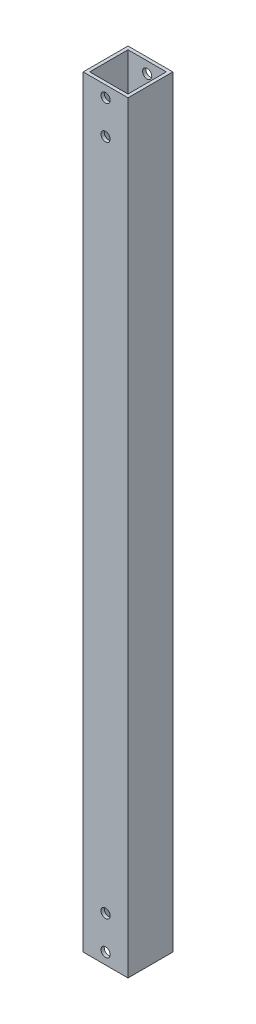
SolidWorks part; units mm, degrees
ref_plane "Front Plane" through (0, 0, 0) normal (0, 0, 1) x (1, 0, 0)
ref_plane "Top Plane" through (0, 0, 0) normal (0, 1, 0) x (1, 0, 0)
ref_plane "Right Plane" through (0, 0, 0) normal (1, 0, 0) x (0, 0, -1)
sketch "Sketch1" plane through (0, 0, 0) normal (0, 1, 0) x (1, 0, 0)
  line L0 (1.45, 18.55) -> (18.55, 18.55)
  line L1 (0, 0) -> (20, 0)
  line L2 (0, 0) -> (0, 20)
  line L3 (0, 20) -> (20, 20)
  line L4 (20, 0) -> (20, 20)
  line L5 (18.55, 1.45) -> (18.55, 18.55)
  line L6 (1.45, 1.45) -> (18.55, 1.45)
  line L7 (1.45, 1.45) -> (1.45, 18.55)
  dimension "D1" = 20
  dimension "D2" = 1.45
extrude "Boss-Extrude1" add sketch "Sketch1" along normal blind 340
sketch "Sketch2" plane through (0, 0, -20) normal (0, 0, -1) x (-1, 0, 0)
  line L0 (-20, 340) -> (0, 340) construction
  line L1 (-20, 340) -> (-20, 0) construction
  line L2 (-20, 0) -> (0, 0) construction
  circle A0 centre (-10, 335) radius 2.05
  circle A1 centre (-10, 320) radius 2.05
  circle A2 centre (-10, 20) radius 2.05
  circle A3 centre (-10, 5) radius 2.05
  point P12 (0, 0)
  dimension "D1" = 15
  dimension "D2" = 4.1
  dimension "D3" = 5
  dimension "D4" = 10
  dimension "D5" = 15
  dimension "D6" = 5
extrude "Cut-Extrude1" cut sketch "Sketch2" against normal through all
